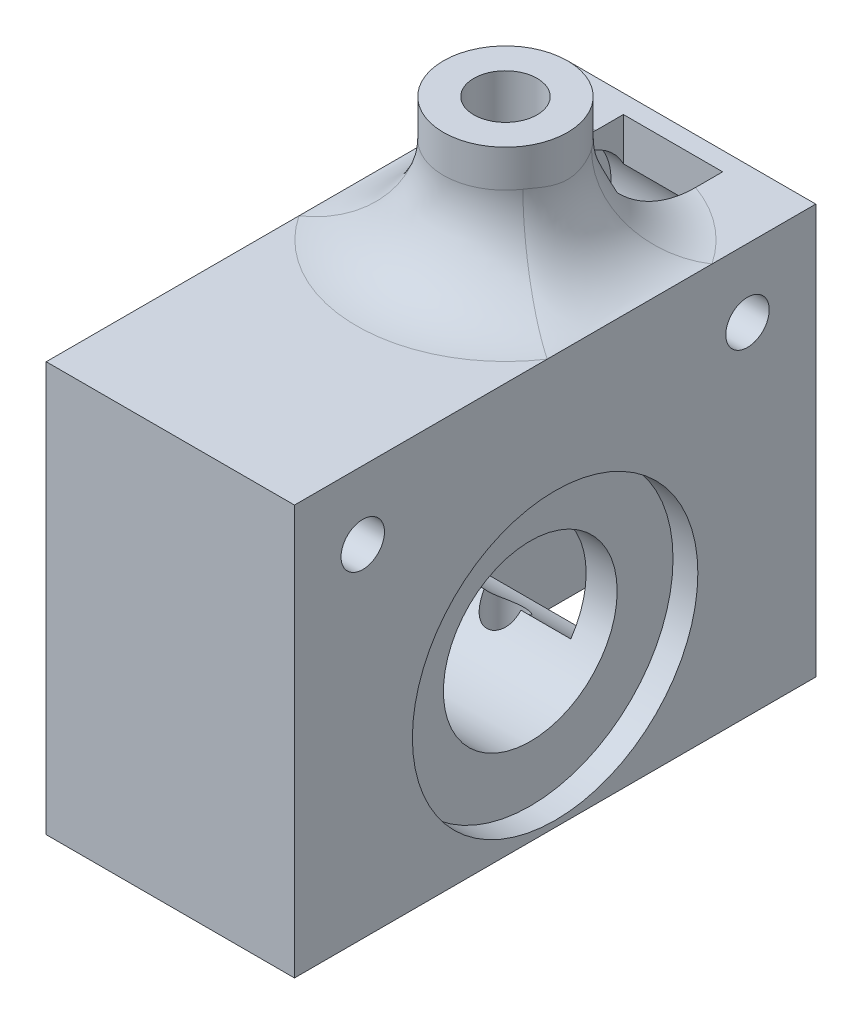
SolidWorks part; units mm, degrees
ref_plane "Front Plane" through (0, 0, 0) normal (0, 0, 1) x (1, 0, 0)
ref_plane "Top Plane" through (0, 0, 0) normal (0, 1, 0) x (1, 0, 0)
ref_plane "Right Plane" through (0, 0, 0) normal (1, 0, 0) x (0, 0, -1)
sketch "Sketch1" plane through (0, 0, 0) normal (1, 0, 0) x (0, 0, -1)
  line L1 (-21, -12) -> (21, -12)
  line L2 (-21, -12) -> (-21, 21)
  line L3 (-21, 21) -> (21, 21)
  line L4 (21, -12) -> (21, 21)
  line L5 (15.5, 15.5) -> (21, 15.5) construction
  line L6 (15.5, 15.5) -> (15.5, 21) construction
  line L7 (15.5, 21) -> (21, 21)
  line L8 (21, 15.5) -> (21, 21)
  line L9 (-15.5, 15.5) -> (-21, 15.5) construction
  line L10 (-15.5, 15.5) -> (-15.5, 21) construction
  line L11 (-15.5, 21) -> (-21, 21)
  line L12 (-21, 15.5) -> (-21, 21)
  circle A0 centre (0, 0) radius 7
  circle A2 centre (15.5, 15.5) radius 1.75
  circle A4 centre (-15.5, 15.5) radius 1.75
  point P10 (0, -12)
  dimension "D4" = 14
  dimension "D7" = 3.5
  dimension "D1" = 42
  dimension "D2" = 33
  dimension "D3" = 12
  dimension "D5" = 5.5
extrude "Boss-Extrude1" add sketch "Sketch1" along normal mid plane 20 contours L1 L4 L3 L2 A4 A2 A0 region at (0, 1.75, 20.4659)
sketch "Sketch2" plane through (10, 0, 0) normal (1, 0, 0) x (0, 0, -1)
  circle A0 centre (0, 0) radius 11.5
  dimension "D1" = 23
extrude "Cut-Extrude1" cut sketch "Sketch2" against normal blind 2
sketch "Sketch3" plane through (0, 21, 0) normal (0, 1, 0) x (1, 0, 0)
  line L1 (10, -21) -> (-10, -21) construction
  line L2 (0, -23.1) -> (0, 23.1) construction
  circle A0 centre (0, 6) radius 1.5
  circle A1 centre (0, 6) radius 5
  circle A2 centre (0, 6) radius 2.55
  dimension "D1" = 3
  dimension "D2" = 10
  dimension "D3" = 5.1
  dimension "D4" = 27
extrude "Cut-Extrude2" cut sketch "Sketch3" against normal through all both and the other way through all contours A0 region at (0, 21, -6)
extrude "Boss-Extrude2" add sketch "Sketch3<3>" along normal blind 10 contours A1 A2 region at (-4.8586, 21, -6)
sketch "Sketch3<3>" plane through (0, 21, 0) normal (0, 1, 0) x (1, 0, 0) same geometry as "Sketch3"
fillet "Fillet1" radius 7 1 edges at (0, 21, -1)
sketch "Sketch4" plane through (0, 0, 0) normal (1, 0, 0) x (0, 0, -1)
  line L0 (21, -12) -> (21, 21) construction
  line L1 (11, 31) -> (19.5, 31)
  line L2 (11, 31) -> (11, 17.5616)
  line L3 (11, 17.5616) -> (19.5, 17.5616)
  line L4 (19.5, 31) -> (19.5, 17.5616)
  line L5 (12.3771, 13.4239) -> (10.1218, 4.749) construction
  line L6 (12.1389, 12.5078) -> (10.8803, 7.6666)
  line L8 (17.7976, 16.4855) -> (21, 9.0193)
  line L9 (15.5, 15.5) -> (17.7976, 16.4855) construction
  line L10 (21, -6.3174) -> (21, -12)
  line L11 (21, -12) -> (10.9554, -12)
  line L12 (-21, -12) -> (21, -12) construction
  line L13 (10.9554, -12) -> (8.9677, -6.0309)
  line L14 (3.1658, 11.3929) -> (15.5, 15.5) construction
  circle A0 centre (15.5, 15.5) radius 4.5
  arc A2 (11, 0.6676) -> (29.3256, 8.4927) centre (15.5, 15.5) ccw construction
  arc A3 (8.9677, -6.0309) -> (35.5695, 5.3282) centre (15.5, 15.5) ccw
  arc A4 (13.0323, 7.3661) -> (23.0818, 11.6573) centre (15.5, 15.5) ccw
  arc A5 (13.0323, 7.3661) -> (8.9677, -6.0309) centre (11, 0.6676) ccw
  arc A6 (35.5695, 5.3282) -> (23.0818, 11.6573) centre (29.3256, 8.4927) ccw
  circle A7 centre (0, 0) radius 6 construction
  point P12 (21.5869, 1.2452)
  dimension "D1" = 9
  dimension "D3" = 7
  dimension "D4" = 15.5
  dimension "D5" = 5
  dimension "D6" = 80
  dimension "D2" = 1.5
  dimension "D7" = 2.5
  dimension "D8" = 13
extrude "Cut-Extrude3" cut sketch "Sketch4" against normal mid plane 11 contours A5 A4 L8 A0 L6 | A0 | L3 A0 | A3 L13 L11 L10 | A4 A6 A3 A5 region at (0, 14.6414, -15.5) region at (0, 18.5639, -15.5) region at (0, 9.4721, -15.9021) region at (0, -9.2876, -15.4764)
extrude "Cut-Extrude4" cut sketch "Sketch4<5>" against normal mid plane 8 contours A0 L4 L1 L2 L3 region at (0, 25.0745, -15.2153)
sketch "Sketch4<5>" plane through (0, 0, 0) normal (1, 0, 0) x (0, 0, -1) same geometry as "Sketch4"
chamfer "Chamfer1" distance 0.6 angle 35 2 edges at (0, 12.5078, -12.1389) (0, 13.0468, -19.2725) first distance on face at (0, 16.3822, -15.4333)
